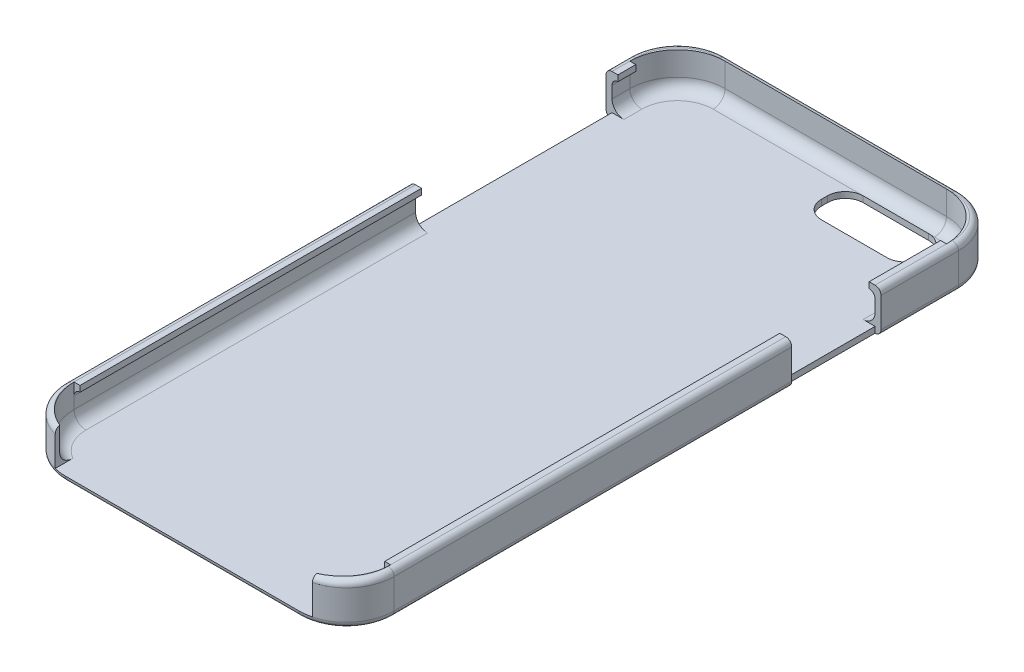
SolidWorks part; units mm, degrees
ref_plane "Front Plane" through (0, 0, 0) normal (0, 0, 1) x (1, 0, 0)
ref_plane "Top Plane" through (0, 0, 0) normal (0, 1, 0) x (1, 0, 0)
ref_plane "Right Plane" through (0, 0, 0) normal (1, 0, 0) x (0, 0, -1)
sketch "Sketch1" plane through (0, 0, 0) normal (0, 1, 0) x (1, 0, 0)
  line L1 (-35.052, 70.358) -> (35.052, 70.358)
  line L2 (-35.052, 70.358) -> (-35.052, -70.358)
  line L3 (-35.052, -70.358) -> (35.052, -70.358)
  line L4 (35.052, 70.358) -> (35.052, -70.358)
  line L5 (-35.052, 70.358) -> (35.052, -70.358) construction
  line L6 (-35.052, -70.358) -> (35.052, 70.358) construction
  point P0 (0, 0)
  dimension "D1" = 70.104
  dimension "D2" = 140.716
extrude "Boss-Extrude1" add sketch "Sketch1" along normal blind 1.27
sketch "Sketch2" plane through (0, 1.27, 0) normal (0, 1, 0) x (1, 0, 0)
  line L0 (-35.052, -70.358) -> (0, -70.358)
  line L1 (-35.052, -70.358) -> (35.052, -70.358) construction
  line L2 (-35.052, 70.358) -> (-35.052, -70.358)
  line L3 (-35.052, 70.358) -> (35.052, 70.358)
  line L4 (-33.782, 69.088) -> (-33.782, -69.088)
  line L5 (0, -70.358) -> (35.052, -70.358)
  line L6 (-33.782, -69.088) -> (33.782, -69.088)
  line L7 (35.052, 70.358) -> (35.052, -70.358)
  line L9 (33.782, 69.088) -> (33.782, -69.088)
  line L12 (-33.782, 69.088) -> (33.782, 69.088)
  dimension "D1" = 1.27
  dimension "D2" = 1.27
  dimension "D3" = 1.27
  dimension "D5" = 1.27
extrude "Boss-Extrude2" add sketch "Sketch2" along normal blind 7.62
sketch "Sketch3" plane through (-35.052, 0, 0) normal (-1, 0, 0) x (0, 0, 1)
  line L0 (-70.358, 8.89) -> (70.358, 8.89) construction
  line L1 (-55.118, 8.89) -> (-13.208, 8.89)
  line L2 (-55.118, 8.89) -> (-55.118, 1.27)
  line L3 (-55.118, 1.27) -> (-13.208, 1.27)
  line L4 (-13.208, 8.89) -> (-13.208, 1.27)
  line L5 (-70.358, 8.89) -> (-70.358, 0) construction
  line L6 (-70.358, 0) -> (70.358, 0) construction
  dimension "D1" = 15.24
  dimension "D2" = 57.15
  dimension "D3" = 1.27
extrude "Cut-Extrude1" cut sketch "Sketch3" against normal blind 1.27
sketch "Sketch5" plane through (35.052, 0, 0) normal (1, 0, 0) x (0, 0, -1)
  line L0 (-70.358, 8.89) -> (70.358, 8.89) construction
  line L1 (24.638, 8.89) -> (43.688, 8.89)
  line L2 (24.638, 8.89) -> (24.638, 1.27)
  line L3 (24.638, 1.27) -> (43.688, 1.27)
  line L4 (43.688, 8.89) -> (43.688, 1.27)
  line L5 (70.358, 8.89) -> (70.358, 0) construction
  line L6 (-70.358, 0) -> (70.358, 0) construction
  dimension "D1" = 26.67
  dimension "D2" = 45.72
  dimension "D3" = 1.27
extrude "Cut-Extrude2" cut sketch "Sketch5" against normal blind 1.27
sketch "Sketch6" plane through (0, 0, 70.358) normal (0, 0, 1) x (1, 0, 0)
  line L1 (-35.052, 8.89) -> (35.052, 8.89) construction
  line L2 (-27.432, 8.89) -> (27.432, 8.89)
  line L3 (-27.432, 8.89) -> (-27.432, 1.27)
  line L4 (-27.432, 1.27) -> (27.432, 1.27)
  line L8 (27.432, 8.89) -> (27.432, 1.27)
  line L9 (-35.052, 8.89) -> (-35.052, 0) construction
  line L10 (35.052, 8.89) -> (35.052, 0) construction
  line L11 (-35.052, 0) -> (35.052, 0) construction
  dimension "D1" = 7.62
  dimension "D2" = 7.62
  dimension "D3" = 1.27
extrude "Cut-Extrude3" cut sketch "Sketch6" against normal blind 1.27
sketch "Sketch7" plane through (0, 0, 0) normal (0, -1, 0) x (1, 0, 0)
  line L0 (35.052, 70.358) -> (35.052, -70.358) construction
  line L1 (26.162, -57.658) -> (4.572, -57.658)
  line L2 (26.162, -57.658) -> (26.162, -66.548)
  line L3 (26.162, -66.548) -> (4.572, -66.548)
  line L4 (4.572, -57.658) -> (4.572, -66.548)
  line L5 (35.052, -70.358) -> (-35.052, -70.358) construction
  dimension "D1" = 8.89
  dimension "D2" = 30.48
  dimension "D3" = 3.81
  dimension "D4" = 12.7
extrude "Cut-Extrude4" cut sketch "Sketch7" against normal blind 1.27
fillet "Fillet1" radius 10.16 4 edges at (33.782, 5.08, -69.088) (-33.782, 5.08, -69.088) (-33.782, 5.08, 69.088) (33.782, 5.08, 69.088)
fillet "Fillet2" radius 10.16 4 edges at (-35.052, 4.445, -70.358) (35.052, 4.445, -70.358) (35.052, 4.445, 70.358) (-35.052, 4.445, 70.358)
sketch "Sketch8" plane through (-33.782, 0, 0) normal (1, 0, 0) x (0, 0, -1)
  line L0 (58.928, 1.27) -> (58.928, 8.89) construction
  line L1 (55.118, 8.89) -> (58.928, 8.89)
  line L2 (55.118, 8.89) -> (55.118, 7.62)
  line L3 (55.118, 7.62) -> (58.928, 7.62)
  line L4 (58.928, 8.89) -> (58.928, 7.62)
  dimension "D1" = 1.27
extrude "Boss-Extrude3" add sketch "Sketch8" along normal blind 1.27
sketch "Sketch13" plane through (0, 0, -69.088) normal (0, 0, 1) x (1, 0, 0)
  line L0 (23.622, 1.27) -> (23.622, 8.89) construction
  line L1 (-23.622, 8.89) -> (23.622, 8.89)
  line L2 (-23.622, 8.89) -> (-23.622, 7.62)
  line L3 (-23.622, 7.62) -> (23.622, 7.62)
  line L4 (23.622, 8.89) -> (23.622, 7.62)
  dimension "D1" = 1.27
extrude "Boss-Extrude6" [suppressed] add sketch "Sketch13" along normal blind 1.27
sketch "Sketch14" plane through (33.782, 0, 0) normal (-1, 0, 0) x (0, 0, 1)
  line L0 (-43.688, 1.27) -> (-43.688, 8.89) construction
  line L1 (-58.928, 8.89) -> (-43.688, 8.89)
  line L2 (-58.928, 8.89) -> (-58.928, 7.62)
  line L3 (-58.928, 7.62) -> (-43.688, 7.62)
  line L4 (-43.688, 8.89) -> (-43.688, 7.62)
  dimension "D1" = 1.27
extrude "Boss-Extrude7" add sketch "Sketch14" along normal blind 1.27
sketch "Sketch19" plane through (33.782, 0, 0) normal (-1, 0, 0) x (0, 0, 1)
  line L1 (59.6694, 1.27) -> (59.6694, 8.89) construction
  line L2 (-24.638, 8.89) -> (59.6694, 8.89)
  line L3 (-24.638, 8.89) -> (-24.638, 7.62)
  line L4 (-24.638, 7.62) -> (59.6694, 7.62)
  line L5 (59.6694, 8.89) -> (59.6694, 7.62)
  dimension "D1" = 1.27
extrude "Boss-Extrude8" add sketch "Sketch19" along normal blind 1.27
sketch "Sketch20" plane through (-33.782, 0, 0) normal (1, 0, 0) x (0, 0, -1)
  line L1 (-59.6694, 8.89) -> (-59.6694, 1.27) construction
  line L2 (13.208, 8.89) -> (-59.6694, 8.89)
  line L3 (13.208, 8.89) -> (13.208, 7.62)
  line L4 (13.208, 7.62) -> (-59.6694, 7.62)
  line L5 (-59.6694, 8.89) -> (-59.6694, 7.62)
  dimension "D1" = 1.27
extrude "Boss-Extrude9" add sketch "Sketch20" along normal blind 1.27
fillet "Fillet9" radius 3.81 4 edges at (26.162, 0.635, -57.658) (26.162, 0.635, -66.548) (4.572, 0.635, -66.548) (4.572, 0.635, -57.658)
fillet "Fillet12" radius 1.27 8 edges at (32.0762, 0, 67.3822) (0, 0, 70.358) (-32.0762, 0, 67.3822) (-35.052, 0, 0) (-32.0762, 0, -67.3822) (0, 0, -70.358) (32.0762, 0, -67.3822) (35.052, 0, 0)
fillet "Fillet15" radius 1.27 7 edges at (32.9242, 8.89, 66.4197) (-32.9242, 8.89, 66.4197) (35.052, 8.89, 17.78) (32.0762, 8.89, -67.3822) (-35.052, 8.89, 23.495) (-32.0762, 8.89, -67.3822) (0, 8.89, -70.358)
fillet "Fillet16" radius 2.54 9 edges at (33.782, 1.27, -51.308) (30.8062, 1.27, -66.1122) (-33.782, 1.27, -57.023) (-30.8062, 1.27, -66.1122) (33.782, 1.27, 17.5157) (-33.782, 1.27, 23.2307) (0, 1.27, -69.088) (32.0462, 1.27, 65.349) (-32.0462, 1.27, 65.349)
sketch "Sketch28" plane through (0, 1.27, 0) normal (0, 1, 0) x (1, 0, 0)
  line L0 (31.242, 24.638) -> (35.052, 24.638) construction
  line L1 (35.052, 43.688) -> (33.782, 43.688)
  line L2 (35.052, 43.688) -> (35.052, 24.638)
  line L3 (35.052, 24.638) -> (33.782, 24.638)
  line L4 (33.782, 43.688) -> (33.782, 24.638)
  line L5 (-31.242, 13.208) -> (-35.052, 13.208) construction
  line L6 (-35.052, 55.118) -> (-33.782, 55.118)
  line L7 (-35.052, 55.118) -> (-35.052, 13.208)
  line L8 (-35.052, 13.208) -> (-33.782, 13.208)
  line L9 (-33.782, 55.118) -> (-33.782, 13.208)
  dimension "D1" = 1.27
  dimension "D2" = 1.27
extrude "Cut-Extrude10" cut sketch "Sketch28" against normal blind 1.27
fillet "Fillet18" radius 1.27 4 edges at (33.782, 7.62, -51.308) (-33.782, 7.62, -57.023) (33.782, 7.62, 17.5157) (-33.782, 7.62, 23.2307)
